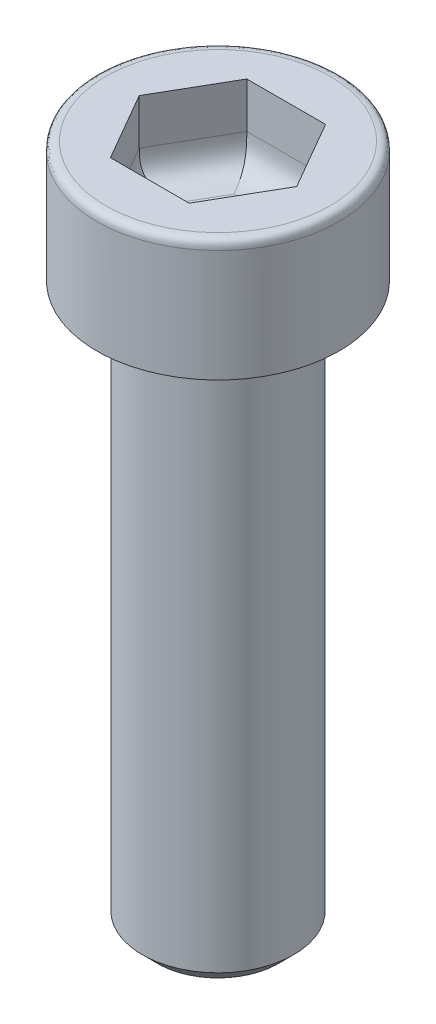
SolidWorks part; units mm, degrees
ref_plane "Front Plane" through (0, 0, 0) normal (0, 0, 1) x (1, 0, 0)
ref_plane "Top Plane" through (0, 0, 0) normal (0, 1, 0) x (1, 0, 0)
ref_plane "Right Plane" through (0, 0, 0) normal (1, 0, 0) x (0, 0, -1)
sketch "Sketch1" plane through (0, 0, 0) normal (0, 0, 1) x (1, 0, 0)
  line L0 (0, 0) -> (0, 45)
  line L1 (0, 45) -> (8, 45)
  line L2 (8, 45) -> (8, 37)
  line L3 (8, 37) -> (5, 37)
  line L4 (5, 37) -> (5, 0)
  line L5 (5, 0) -> (0, 0)
  dimension "D1" = 5
  dimension "D2" = 8
  dimension "D3" = 8
  dimension "D4" = 45
revolve "Revolve1" add sketch "Sketch1" angle 360 about L0
sketch "Sketch2" plane through (0, 45, 0) normal (0, 1, 0) x (1, 0, 0)
  line L1 (-5.1962, 0) -> (-2.5981, -4.5)
  line L2 (-2.5981, -4.5) -> (2.5981, -4.5)
  line L3 (2.5981, -4.5) -> (5.1962, 0)
  line L4 (5.1962, 0) -> (2.5981, 4.5)
  line L5 (2.5981, 4.5) -> (-2.5981, 4.5)
  line L6 (-2.5981, 4.5) -> (-5.1962, 0)
  circle A0 centre (0, 0) radius 4.5 construction
  dimension "D1" = 9
extrude "Cut-Extrude1" cut sketch "Sketch2" against normal blind 5
fillet "Fillet1" radius 2 6 edges at (0, 40, -4.5) (3.8971, 40, -2.25) (3.8971, 40, 2.25) (0, 40, 4.5) (-3.8971, 40, 2.25) (-3.8971, 40, -2.25) curvature continuous yes
fillet "Fillet2" radius 0.6 1 edges at (0, 45, -8) curvature continuous yes
ref_axis "Axis1" through (0, 37, 0) along (0, -1, 0)
chamfer "Chamfer1" distance 1 angle 45 1 edges at (0, 0, -5)
